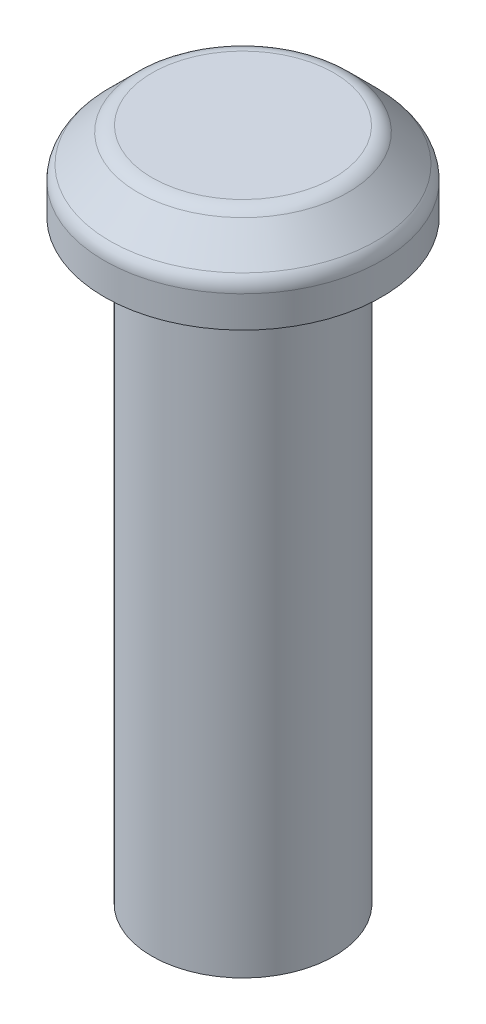
SolidWorks part; units mm, degrees
ref_plane "Front Plane" through (0, 0, 0) normal (0, 0, 1) x (1, 0, 0)
ref_plane "Top Plane" through (0, 0, 0) normal (0, 1, 0) x (1, 0, 0)
ref_plane "Right Plane" through (0, 0, 0) normal (1, 0, 0) x (0, 0, -1)
sketch "Sketch1" plane through (0, 0, 0) normal (0, 1, 0) x (1, 0, 0)
  circle A0 centre (0, 0) radius 2.3
  dimension "D1" = 4.6
extrude "Boss-Extrude1" add sketch "Sketch1" along normal blind 15
sketch "Sketch2" plane through (0, 15, 0) normal (0, 1, 0) x (1, 0, 0)
  circle A0 centre (0, 0) radius 3.5
  dimension "D1" = 7
extrude "Boss-Extrude2" add sketch "Sketch2" along normal blind 2
chamfer "Chamfer1" distance 1 angle 45 1 edges at (0, 17, 3.5)
fillet "Fillet1" radius 0.5 2 edges at (0, 16, 3.5) (0, 17, 2.5)
